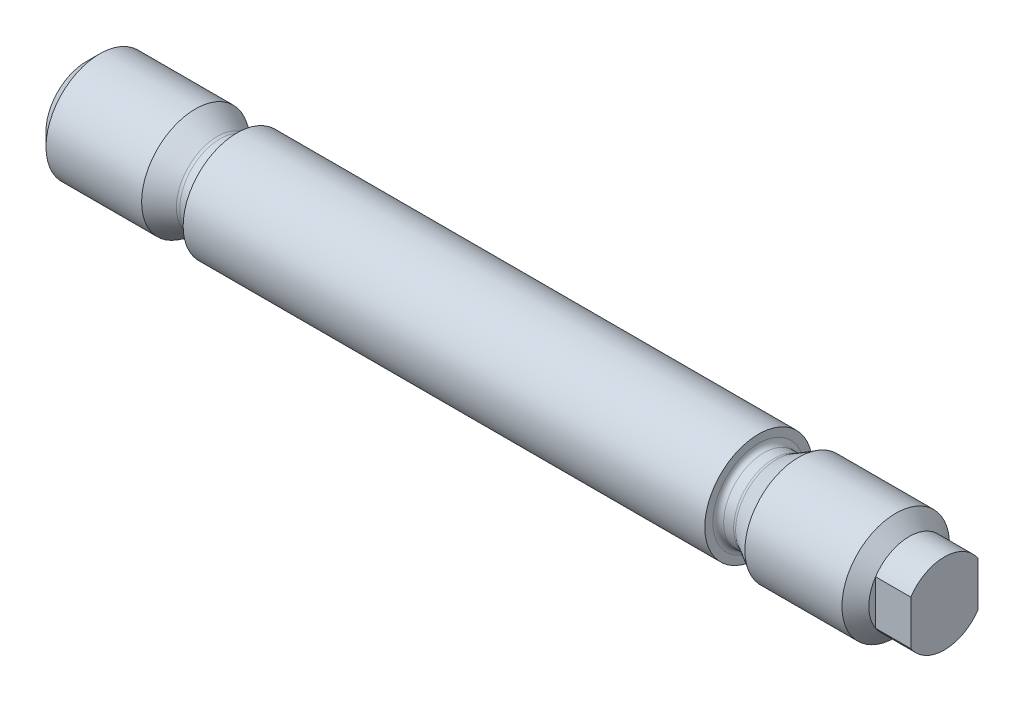
SolidWorks part; units mm, degrees
revolve "BaseBody" add sketch "BodySke" angle 360 about L14 other way angle 60
sketch "BodySke" plane through (0, 0, 0) normal (0, 0, 1) x (1, 0, 0)
  line L0 (19.5, 6.1072) -> (16.2215, 8)
  line L1 (16.2215, 8) -> (2, 8)
  line L2 (22.4, 8) -> (22.4, 6.8)
  line L3 (21.6, 6) -> (19.9, 6)
  line L5 (2, 8) -> (0, 6)
  line L7 (100, 8) -> (100, 6.8)
  line L8 (100.8, 6) -> (102.2856, 6)
  line L9 (102.6856, 6.1072) -> (105.9641, 8)
  line L10 (105.9641, 8) -> (120.4, 8)
  line L11 (120.4, 8) -> (122.4, 6)
  line L12 (122.4, 6) -> (122.4, 0)
  line L13 (122.4, 0) -> (0, 0)
  line L14 (-3.175, 0) -> (101.6, 0) construction
  line L15 (108.7794, -6) -> (122.4, -6) construction
  line L16 (100, -6) -> (102.5, -6) construction
  line L17 (37.0699, -8) -> (100, -8) construction
  line L18 (0, 6) -> (0, 0)
  line L19 (22.4, 8) -> (100, 8)
  line L20 (104.5, 10.8514) -> (104.5, -6.5014) construction
  line L21 (100, 10.2761) -> (100, -5.5735) construction
  arc A0 (19.9, 6) -> (19.5, 6.1072) centre (19.9, 6.8) cw
  arc A1 (22.4, 6.8) -> (21.6, 6) centre (21.6, 6.8) cw
  arc A2 (102.2856, 6) -> (102.6856, 6.1072) centre (102.2856, 6.8) ccw
  arc A3 (100, 6.8) -> (100.8, 6) centre (100.8, 6.8) ccw
  point P26 (102.5, 6)
  point P29 (100, 6)
  dimension "Advance" = 2
  dimension "Shoulder_neck_width" = 2.5
  dimension "Length" = 100
  dimension "Thread_len" = 22.4
cosmetic thread "ThreadCosmetic" [suppressed] parameters "Thread_minor"=12
cosmetic thread "ThreadCosmeticStud" [suppressed] parameters "Thrd_Minor"=12
ref_plane "Plane1" through (0, 0, 0) normal (0, 0, 1) x (1, 0, 0)
ref_plane "Plane2" through (0, 0, 0) normal (0, 1, 0) x (1, 0, 0)
ref_plane "Plane3" through (0, 0, 0) normal (1, 0, 0) x (0, 0, -1)
sketch "ThdSchSke" plane through (0, 0, 0) normal (0, 0, 1) x (1, 0, 0)
  line L0 (104.5, -6) -> (103.0996, -8)
  line L1 (104.5, -6) -> (105.9004, -8)
  line L2 (105.9004, -8) -> (105.9004, -10)
  line L3 (-3.175, 0) -> (5.1513, 0) construction
  line L5 (105.9004, -10) -> (103.0996, -10)
  line L6 (103.0996, -10) -> (103.0996, -8)
  line L7 (122.4, -6) -> (122.4, 6) construction
  dimension "Thread_minor" = 12
  dimension "Diameter" = 16
  dimension "Start" = 17.9
  dimension "SideAngle" = 55
  dimension "VeeAngle" = 70
  dimension "Overcut" = 20
revolve "ThreadSchematic" [suppressed] cut sketch "ThdSchSke" angle 360 about L3
pattern_linear "ThdSchPat" [suppressed]
sketch "ThdSchSketStud" plane through (0, 0, 0) normal (0, 0, 1) x (1, 0, 0)
  line L0 (17.9, -6) -> (16.4996, -8)
  line L1 (17.9, -6) -> (19.3004, -8)
  line L2 (19.3004, -8) -> (19.3004, -10)
  line L3 (-3.175, 0) -> (5.1513, 0) construction
  line L5 (19.3004, -10) -> (16.4996, -10)
  line L6 (16.4996, -10) -> (16.4996, -8)
  line L7 (0, 6) -> (0, -6) construction
  dimension "Thread_minor" = 12
  dimension "Diameter" = 16
  dimension "SideAngle" = 55
  dimension "VeeAngle" = 70
  dimension "Overcut" = 20
revolve "ThreadSchematicStud" [suppressed] cut sketch "ThdSchSketStud" angle 360 about L3
pattern_linear "ThdSchPatStud" [suppressed]
sketch "DogPointSke" plane through (122.4, 0, 0) normal (1, 0, 0) x (0, 0, -1)
  line L0 (-5, 3.3166) -> (-5, -3.3166)
  line L1 (5, 3.3166) -> (5, -3.3166)
  line L2 (0, -9.525) -> (0, 9.525) construction
  arc A0 (-5, -3.3166) -> (5, -3.3166) centre (0, 0) ccw
  arc A2 (5, 3.3166) -> (-5, 3.3166) centre (0, 0) ccw
  dimension "Point_Dia" = 12
  dimension "Dog_Width" = 10
extrude "DogPoint" add sketch "DogPointSke" along normal blind 5.24
equation "\"Thread_len@BodySke\" = \"Thread_nom@BodySke\""
equation "\"Studend_length@BodySke\" = \"Thread_len@BodySke\""
equation "\"Thread_minor@ThreadCosmetic\" = \"Minor_dia@BodySke\""
equation "\"Thrd_Minor@ThreadCosmeticStud\" = \"Thread_minor@ThreadCosmetic\""
equation "\"Thread_minor@ThdSchSke\" = \"Minor_dia@BodySke\""
equation "\"Diameter@ThdSchSke\" = \"Thread_dia@BodySke\""
equation "\"Overcut@ThdSchSke\" = \"Thread_dia@BodySke\" * 1.25"
equation "\"Start@ThdSchSke\" = \"Thread_nom@BodySke\"  - \"Thread_neck_width@BodySke\" - \"Advance@BodySke\""
equation "\"Num_threads@ThdSchPat\" = int( \"Start@ThdSchSke\" / \"Advance@BodySke\" + 0.999 ) + 1"
equation "\"Advance@ThdSchPat\" = \"Start@ThdSchSke\" /  ( \"Num_threads@ThdSchPat\" - 1 ) 'relax it"
equation "'  \"Num_threads@ThdSchPat\" = \"Num_threads@ThdSchPat\" - sgn( \"Num_threads@ThdSchPat\" - 1 ) '---chamfered tips only---"
equation "\"Diameter@ThdSchSketStud\" = \"Diameter@ThdSchSke\""
equation "\"Thread_minor@ThdSchSketStud\" = \"Thread_minor@ThdSchSke\""
equation "\"Overcut@ThdSchSketStud\" = \"Overcut@ThdSchSke\""
equation "\"Start_@ThdSchSketStud\" = \"Studend_length@BodySke\" - \"Shoulder_neck_width@BodySke\" - \"Advance@BodySke\""
equation "\"Num_Threads@ThdSchPatStud\" = int ( \"Start_@ThdSchSketStud\" / \"Advance@BodySke\" + 0.999 )  + 1"
equation "\"Advance@ThdSchPatStud\" = \"Start_@ThdSchSketStud\" /  ( \"Num_Threads@ThdSchPatStud\" - 1 ) 'relax it"
